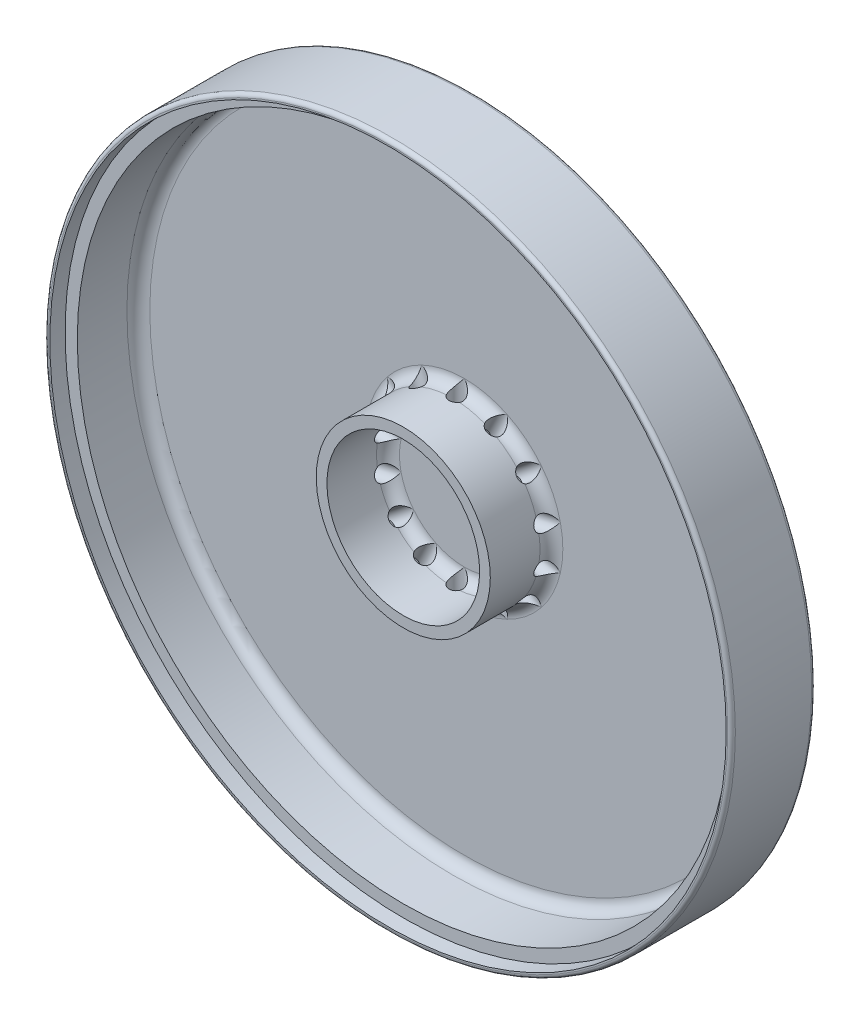
SolidWorks part; units mm, degrees
note: The reader was unsure of these and kept them because the rebuilt part matched: shared geometry of "Sketch1<3>", "Sketch1<4>", "Sketch1<5>".
ref_plane "Front Plane" through (0, 0, 0) normal (0, 0, 1) x (1, 0, 0)
ref_plane "Top Plane" through (0, 0, 0) normal (0, 1, 0) x (1, 0, 0)
ref_plane "Right Plane" through (0, 0, 0) normal (1, 0, 0) x (0, 0, -1)
sketch "Sketch1" plane through (0, 0, 0) normal (0, 0, 1) x (1, 0, 0)
  circle A0 centre (0, 0) radius 90
  circle A1 centre (0, 0) radius 88.6
  circle A2 centre (0, 0) radius 85.4
  circle A3 centre (0, 0) radius 20
  circle A4 centre (0, 0) radius 22.8
  dimension "D1" = 180
  dimension "D5" = 40
  dimension "D2" = 1.4
  dimension "D3" = 3.2
  dimension "D4" = 2.8
extrude "Boss-Extrude1" add sketch "Sketch1" against normal blind 2 contours A2 A4 | A1 A2 | A0 A1 | A3 | A4 A3
extrude "Boss-Extrude2" add sketch "Sketch1<3>" along normal blind 20 contours A0 A1
sketch "Sketch1<3>" plane through (0, 0, 0) normal (0, 0, 1) x (1, 0, 0) same geometry as "Sketch1"
extrude "Boss-Extrude3" add sketch "Sketch1<4>" along normal blind 16 contours A1 A2
sketch "Sketch1<4>" plane through (0, 0, 0) normal (0, 0, 1) x (1, 0, 0) same geometry as "Sketch1"
extrude "Boss-Extrude4" add sketch "Sketch1<5>" along normal blind 16 contours A4 A3
sketch "Sketch1<5>" plane through (0, 0, 0) normal (0, 0, 1) x (1, 0, 0) same geometry as "Sketch1"
sketch "Sketch2" plane through (0, 0, 0) normal (0, 1, 0) x (1, 0, 0)
  line L2 (-20, 0) -> (20, 0) construction
  circle A0 centre (0, -2) radius 2
  dimension "D1" = 4
extrude "Cut-Extrude3" cut sketch "Sketch2" against normal up to next and the other way up to next
fillet "Fillet1" radius 3 1 edges at (85.4, 0, 0)
fillet "Fillet2" radius 3 8 edges at (20, 0, 0) (-22.8, 0, 0) (0.2176, 22.799, 3.9881) (0.2198, 19.9988, 3.9879) (-20, 0, 0) (22.8, 0, 0) (0, -22.8, 4) (0, -20, 4)
fillet "Fillet3" radius 1 1 edges at (90, 0, -2)
fillet "Fillet4" radius 1 1 edges at (90, 0, 20)
pattern_circular "CirPattern1" count 7 over 360 about axis through (0, 0, 16) along (0, 0, -1) of "Cut-Extrude3"
